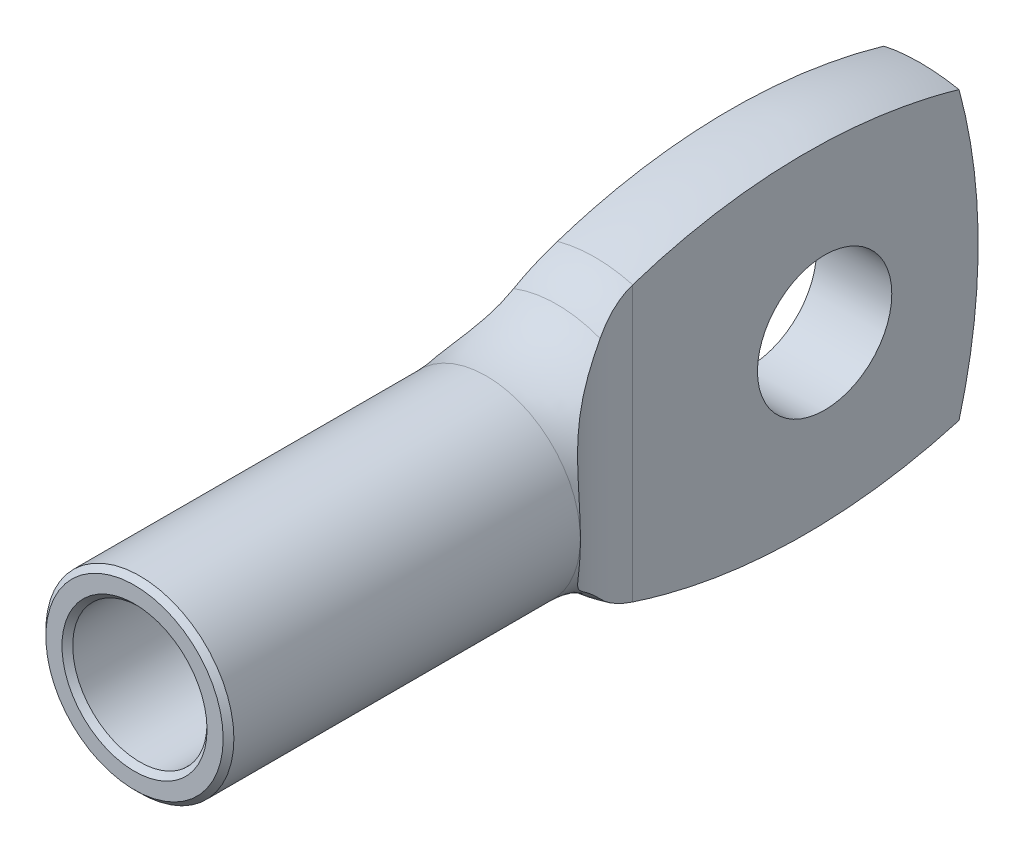
SolidWorks part; units mm, degrees
ref_plane "Front Plane" through (0, 0, 0) normal (0, 0, 1) x (1, 0, 0)
ref_plane "Top Plane" through (0, 0, 0) normal (0, 1, 0) x (1, 0, 0)
ref_plane "Right Plane" through (0, 0, 0) normal (1, 0, 0) x (0, 0, -1)
sketch "Sketch1" plane through (0, 0, 0) normal (0, 0, 1) x (1, 0, 0)
  circle A0 centre (0, 0) radius 4.445
  dimension "OD" = 8.89
extrude "Extrude1" add sketch "Sketch1" against normal blind 38.1
sketch "Sketch2" plane through (0, 0, 0) normal (0, 0, 1) x (1, 0, 0)
  circle A1 centre (0, 0) radius 3.175
  circle A2 centre (0, 0) radius 4.445 construction
  dimension "thread od" = 6.35
curve "Helix/Spiral1" [suppressed] pitch 1.27 height 39.37 turns 31 parameters "pitch"=1.27
sketch "Sketch32" plane through (0, 0, 0) normal (0, 0, 1) x (1, 0, 0)
  circle A0 centre (0, 0) radius 3.175 construction
  circle A1 centre (0, 0) radius 3.175
extrude "Cut-Extrude9" cut sketch "Sketch32" against normal through all
sketch "Sketch3" plane through (0, 0, 0) normal (1, 0, 0) x (0, 0, -1)
  line L0 (-1.1112, 3.175) -> (-0.635, 2.3501)
  line L1 (-0.635, 2.3501) -> (-0.4762, 2.3501)
  line L2 (-0.4762, 2.3501) -> (0, 3.175)
  line L3 (-1.1112, 3.175) -> (0, 3.175)
  line L4 (-0.5556, 3.175) -> (-0.5556, 2.3501) construction
  line L5 (-0.8731, 2.7626) -> (-0.2381, 2.7626) construction
  line L7 (0, 3.175) -> (0, -3.175) construction
  dimension "D1" = 0.1588
  dimension "D2" = 0.635
  dimension "D3" = 60
sweep "Sweep1" [suppressed] add profiles "Sketch3" path "Helix/Spiral1"
sketch "Sketch33" plane through (0, 0, 0) normal (0, 0, 1) x (1, 0, 0)
  circle A1 centre (0, 0) radius 4.445
  circle A2 centre (0, 0) radius 4.445
  dimension "D1" = 0
extrude "Cut-Extrude10" [suppressed] cut sketch "Sketch33" along normal through all
sketch "Sketch34" plane through (0, 0, 0) normal (0, 0, 1) x (1, 0, 0)
  circle A2 centre (0, 0) radius 3.429
  circle A3 centre (0, 0) radius 3.429
  dimension "D1" = 0.254
extrude "Cut-Extrude11" cut sketch "Sketch34" against normal blind 1.524 draft 45
chamfer "Chamfer1" distance 0.254 angle 45 1 edges at (4.445, 0, 0)
sketch "Sketch29" plane through (0, 0, 0) normal (1, 0, 0) x (0, 0, -1)
  line L0 (0, 0) -> (38.1, 0) construction
  line L2 (16.3286, 0) -> (16.3286, 2.3501)
  line L3 (16.3286, 2.3501) -> (16.3286, 4.445)
  line L4 (38.1, 0) -> (38.1, 6.731)
  line L5 (16.3286, 4.445) -> (16.6302, 4.445)
  line L6 (38.1, 8.001) -> (16.3286, 8.001) construction
  line L7 (38.1, 0) -> (16.3286, 0)
  line L8 (38.1, 4.445) -> (0.254, 4.445) construction
  line L9 (38.1, -4.445) -> (38.1, 4.445) construction
  arc A0 (38.1, 6.731) -> (21.7714, 6.731) centre (29.9357, -18.8763) ccw
  arc A1 (16.6302, 4.445) -> (19.9663, 5.7071) centre (16.6302, 9.4854) ccw
  arc A2 (19.9663, 5.7071) -> (21.7714, 6.731) centre (23.3025, 1.9288) cw
  point P19 (16.3286, 4.445)
  dimension "D3" = 8.001
  dimension "D4" = 1.27
  dimension "D7" = 0.3016
  dimension "D1" = 21.7714
  dimension "D2" = 16.3286
revolve "Revolve2" add sketch "Sketch29" angle 360 about L0
sketch "Sketch30" plane through (0, 0, 0) normal (1, 0, 0) x (0, 0, -1)
  line L0 (38.1, 0) -> (16.3286, 0) construction
  line L1 (44.45, 8.001) -> (36.83, 8.001)
  line L2 (44.45, 8.001) -> (44.45, -8.001)
  line L3 (44.45, -8.001) -> (36.83, -8.001)
  line L4 (38.1, 8.001) -> (16.3286, 8.001) construction
  line L5 (38.1, 0) -> (38.1, 6.731) construction
  line L6 (38.1, 15.0875) -> (30.8429, 15.0875) construction
  line L7 (30.8429, 15.0875) -> (30.8429, 10.1301) construction
  line L8 (30.8429, 10.1301) -> (23.5857, 10.1301) construction
  line L9 (23.5857, 10.1301) -> (23.5857, 5.0233) construction
  line L10 (23.5857, 5.0233) -> (16.3286, 5.0233) construction
  arc A0 (36.83, 8.001) -> (36.83, -8.001) centre (12.2618, 0) cw
  circle A1 centre (30.8429, 0) radius 3.175
  dimension "hole" = 6.35
  dimension "D1" = 1.27
  dimension "D2" = 6.35
extrude "Cut-Extrude7" cut sketch "Sketch30" against normal mid plane 25.4
sketch "Sketch31" plane through (0, 0, 0) normal (0, 1, 0) x (1, 0, 0)
  line L0 (1.778, 38.1) -> (1.778, 21.7714)
  line L1 (6.731, 38.1) -> (-6.731, 38.1) construction
  line L4 (6.731, 21.7714) -> (-6.731, 21.7714) construction
  line L6 (0, 0) -> (0, -4.9117) construction
  line L7 (-4.445, 0) -> (4.445, 0) construction
  line L8 (-1.778, 38.1) -> (-1.778, 21.7714)
  line L9 (1.778, 38.1) -> (14.478, 38.1)
  line L10 (4.445, 16.6302) -> (14.478, 16.6302)
  line L11 (14.478, 16.6302) -> (14.478, 38.1)
  line L12 (-1.778, 38.1) -> (-14.478, 38.1)
  line L13 (-14.478, 38.1) -> (-14.478, 16.6302)
  line L14 (-4.445, 16.6302) -> (-14.478, 16.6302)
  arc A0 (1.778, 21.7714) -> (4.445, 16.6302) centre (8.0669, 21.7714) ccw
  arc A1 (-1.778, 21.7714) -> (-4.445, 16.6302) centre (-8.0669, 21.7714) cw
  dimension "D1" = 3.556
  dimension "D2" = 12.7
extrude "Cut-Extrude8" cut sketch "Sketch31" against normal mid plane 25.4
sketch "Sketch17" plane through (0, 0, 0) normal (1, 0, 0) x (0, 0, -1)
  line L0 (10.795, 3.175) -> (10.795, -3.175) construction
  line L1 (0, -3.175) -> (0, 3.175) construction
  dimension "D1" = 10.795
equation "\"D3@Helix/Spiral1\" = \"screw length@Extrude1\"+\"pitch@Helix/Spiral1\""
equation "\"D1@Sketch3\" = \"pitch@Helix/Spiral1\"*.125"
equation "\"D2@Sketch3\" = \"pitch@Helix/Spiral1\"*.5"
equation "\"D1@Sketch17\" = \"pitch@Helix/Spiral1\"*8.5"
equation "\"D3@Sketch29\" = \"OD@Sketch1\"*1.8/2"
equation "\"D1@Sketch31\" = \"OD@Sketch1\"*.4"
equation "\"D1@Sketch29\" = \"screw length@Extrude1\"/1.75"
equation "\"D2@Sketch29\" = \"D1@Sketch29\"*.750"
